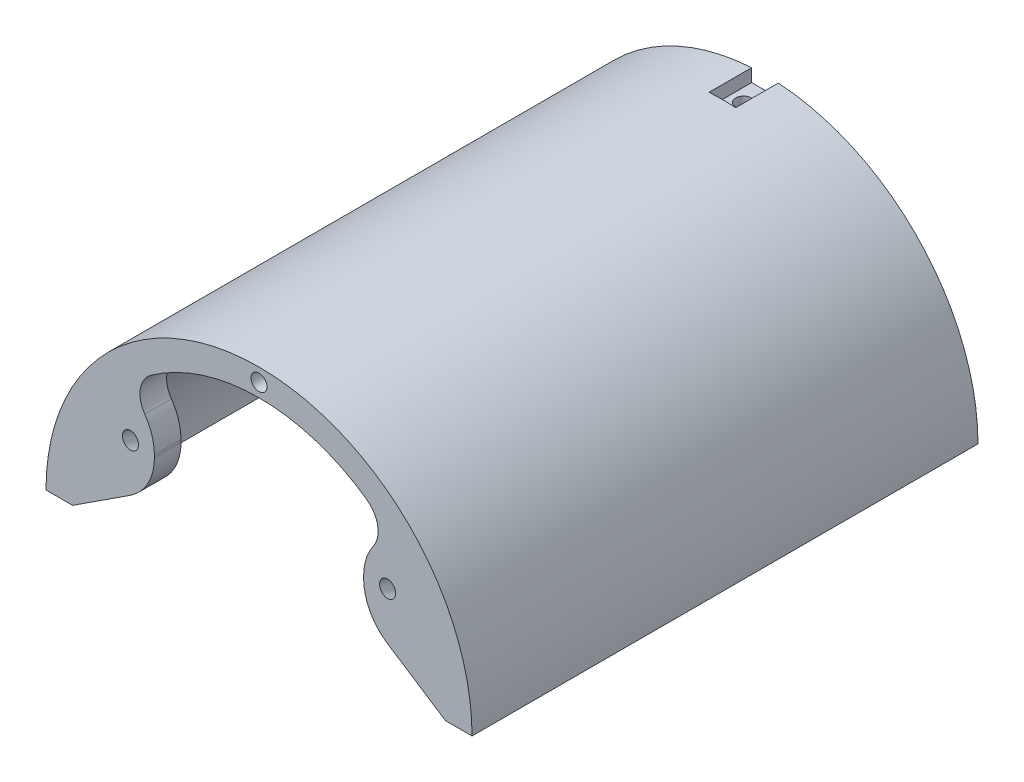
SolidWorks part; units mm, degrees
material "PLA"
ref_plane "Alzado" through (0, 0, 0) normal (0, 0, 1) x (1, 0, 0)
ref_plane "Planta" through (0, 0, 0) normal (0, 1, 0) x (1, 0, 0)
ref_plane "Vista lateral" through (0, 0, 0) normal (1, 0, 0) x (0, 0, -1)
sketch "Croquis1" plane through (0, 0, 0) normal (0, 0, 1) x (1, 0, 0)
  line L0 (-40, 0) -> (40, 0)
  arc A0 (40, 0) -> (-40, 0) centre (0, 0) ccw
  dimension "D1" = 80
extrude "Saliente-Extruir1" add sketch "Croquis1" along normal blind 95
shell "Vaciado1" thickness 5 removed face at (0, 20, 0) removed face at (0, 0, 47.5) removed face at (0, 20, 95)
ref_plane "Plano1" through (0, 40, 0) normal (0, 1, 0) x (1, 0, 0)
sketch "Croquis2" plane through (0, 40, 0) normal (0, 1, 0) x (1, 0, 0)
  line L0 (0, 0) -> (0, -95) construction
  line L1 (40, 0) -> (-40, 0) construction
  line L2 (-40, -95) -> (40, -95) construction
  line L4 (2.5, 8) -> (-2.5, 8)
  line L5 (2.5, 8) -> (2.5, -8)
  line L6 (2.5, -8) -> (-2.5, -8)
  line L7 (-2.5, 8) -> (-2.5, -8)
  line L8 (2.5, 8) -> (-2.5, -8) construction
  line L9 (2.5, -8) -> (-2.5, 8) construction
  dimension "D1" = 5
  dimension "D2" = 16
extrude "Cortar-Extruir1" cut sketch "Croquis2" against normal blind 2.5
sketch "Croquis3" plane through (0, 37.5, 0) normal (0, 1, 0) x (1, 0, 0)
  line L0 (-2.5, -8) -> (2.5, 0) construction
  line L1 (-2.5, 0) -> (2.5, -8) construction
  circle A0 centre (0, -4) radius 1.5
  dimension "D1" = 3
extrude "Cortar-Extruir4" cut sketch "Croquis3" against normal blind 5 contours A0
sketch "Croquis4" plane through (0, 0, 95) normal (0, 0, 1) x (1, 0, 0)
  line L0 (0, 0) -> (0, 40) construction
  line L2 (44, 40) -> (-44, 40) construction
  line L7 (0, 20) -> (34.641, 20) construction
  line L8 (0, 10) -> (38.7298, 10) construction
  line L9 (34.641, 20) -> (19.641, 20)
  line L10 (19.641, 20) -> (19.641, 10)
  line L11 (19.641, 10) -> (38.7298, 10)
  line L12 (0, -22) -> (0, 22) construction
  line L13 (-19.641, 10) -> (-38.7298, 10)
  line L14 (-19.641, 20) -> (-19.641, 10)
  line L15 (-34.641, 20) -> (-19.641, 20)
  arc A5 (40, 0) -> (-40, 0) centre (0, 0) ccw construction
  arc A6 (34.641, 20) -> (38.7298, 10) centre (0, 0) cw
  arc A7 (-34.641, 20) -> (-38.7298, 10) centre (0, 0) ccw
  dimension "D1" = 10
  dimension "D2" = 15
  dimension "D3" = 20
extrude "Saliente-Extruir2" add sketch "Croquis4" along normal mid plane 10
chamfer "Chaflán1" distance 5 angle 20 2 edges at (27.141, 20, 100) (-27.141, 20, 100) first distance on face at (28.248, 15.0347, 100) first distance on face at (-28.248, 15.0347, 100)
sketch "Croquis5" plane through (0, 33.894, 93.1231) normal (0, 0.342, 0.9397) x (1, 0, 0)
  line L0 (-19.641, -14.7857) -> (-28.641, -14.7857) construction
  line L1 (-34.641, -14.7857) -> (-19.641, -14.7857) construction
  line L2 (-24.141, -14.7857) -> (-24.141, -20.1066) construction
  line L3 (-19.641, -20.1066) -> (-37.081, -20.1066) construction
  line L4 (0, -22) -> (0, 22) construction
  circle A0 centre (-24.141, -17.4462) radius 1.5
  circle A1 centre (24.141, -17.4462) radius 1.5
  dimension "D2" = 3
  dimension "D1" = 9
extrude "Cortar-Extruir5" cut sketch "Croquis5" against normal through all
sketch "Croquis6" plane through (0, 0, 0) normal (0, 1, 0) x (1, 0, 0)
  line L0 (40, -95) -> (-40, -95)
  line L1 (-40, -95) -> (-40, -101.5)
  line L2 (-40, -101.5) -> (40, -101.5)
  line L3 (40, -101.5) -> (40, -95)
  dimension "D1" = 6.5
extrude "Cortar-Extruir6" cut sketch "Croquis6" along normal through all
sketch "Croquis7" plane through (0, 0, 95) normal (0, 0, 1) x (1, 0, 0)
  line L0 (19.641, 10) -> (35, 0)
  line L1 (-19.641, 10) -> (-35, 0)
  line L2 (19.641, 10) -> (33.541, 10) construction
  line L3 (-33.541, 10) -> (-19.641, 10) construction
  line L4 (19.641, 10) -> (33.541, 10)
  line L5 (-33.541, 10) -> (-19.641, 10)
  line L6 (-19.641, 20) -> (-28.7228, 20)
  line L13 (-19.641, 20) -> (-24.5686, 24.9276)
  line L14 (0, -22) -> (0, 22) construction
  line L15 (19.641, 20) -> (28.7228, 20)
  line L16 (19.641, 20) -> (24.5686, 24.9276)
  arc A0 (35, 0) -> (33.541, 10) centre (0, 0) ccw construction
  arc A1 (-33.541, 10) -> (-35, 0) centre (0, 0) ccw construction
  arc A2 (35, 0) -> (33.541, 10) centre (0, 0) ccw
  arc A3 (-33.541, 10) -> (-35, 0) centre (0, 0) ccw
  arc A8 (28.7228, 20) -> (-28.7228, 20) centre (0, 0) ccw construction
  arc A9 (-24.5686, 24.9276) -> (-28.7228, 20) centre (0, 0) ccw
  arc A10 (24.5686, 24.9276) -> (28.7228, 20) centre (0, 0) cw
  dimension "D1" = 45
extrude "Saliente-Extruir3" add sketch "Croquis7" against normal blind 5
fillet "Redondeo1" radius 10 4 edges at (19.641, 10, 92.5) (19.641, 20, 92.5) (-19.641, 20, 92.5) (-19.641, 10, 92.5)
fillet "Redondeo2" radius 5 2 edges at (24.5686, 24.9276, 92.5) (-24.5686, 24.9276, 92.5)
sketch "Croquis8" plane through (0, 0, 95) normal (0, 0, 1) x (1, 0, 0)
  line L0 (0, 40) -> (0, 35) construction
  arc A0 (40, 0) -> (-40, 0) centre (0, 0) ccw construction
  arc A1 (20.2514, 28.5461) -> (-20.2514, 28.5461) centre (0, 0) ccw construction
  circle A2 centre (0, 37.5) radius 1.5
  dimension "D1" = 3
extrude "Cortar-Extruir7" cut sketch "Croquis8" against normal blind 5
